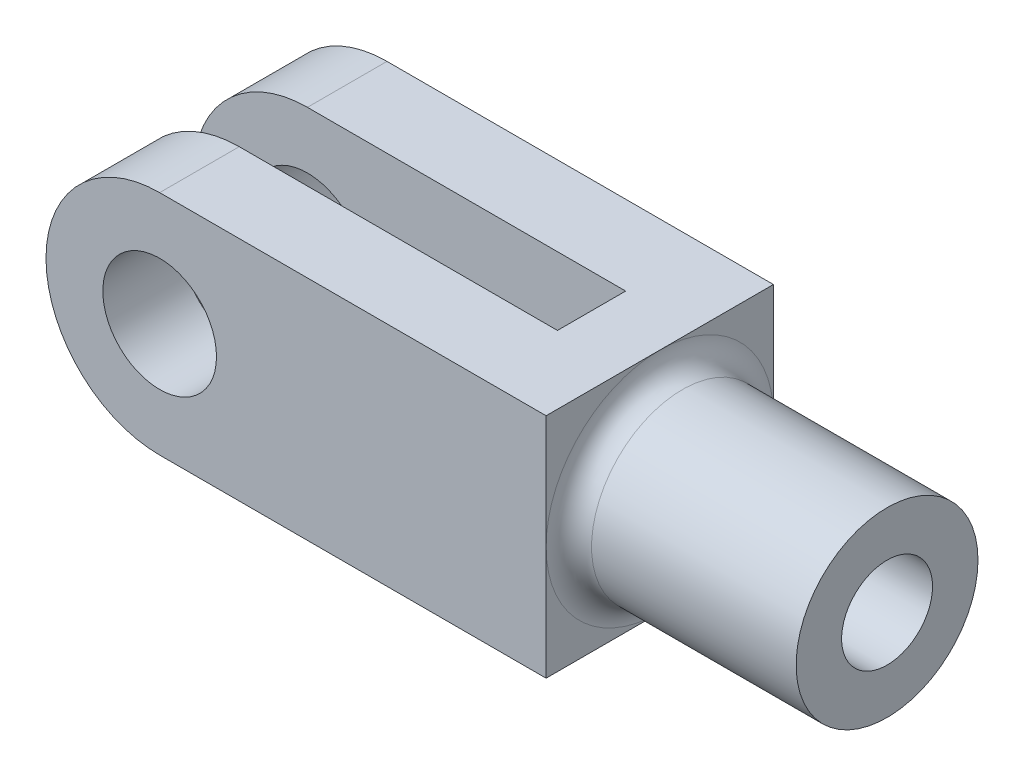
SolidWorks part; units mm, degrees
material "Brass"
ref_plane "Front Plane" through (0, 0, 0) normal (0, 0, 1) x (1, 0, 0)
ref_plane "Top Plane" through (0, 0, 0) normal (0, 1, 0) x (1, 0, 0)
ref_plane "Right Plane" through (0, 0, 0) normal (1, 0, 0) x (0, 0, -1)
sketch "Sketch1" plane through (0, 0, 0) normal (0, 0, 1) x (1, 0, 0)
  line L0 (0, 0) -> (10689.6136, 0) construction
  line L1 (0, 0) -> (0, -10689.6136) construction
  line L3 (17, 5) -> (0, 5)
  line L4 (17, 5) -> (17, -5)
  line L5 (17, -5) -> (0, -5)
  line L7 (17, 5) -> (0, -5) construction
  line L8 (17, -5) -> (0, 5) construction
  circle A0 centre (0, 0) radius 2.5
  arc A1 (0, -5) -> (0, 5) centre (0, 0) cw
  point P7 (8.5, 0)
  point P13 (17, 0)
  dimension "D1" = 5
  dimension "D2" = 17
  dimension "D3" = 10
extrude "Boss-Extrude1" add sketch "Sketch1" along normal mid plane 10 contours A1 L5 L4 L3 A0 region at (7.1805, 0, 0)
sketch "Sketch2" plane through (0, 0, 0) normal (0, 1, 0) x (1, 0, 0)
  line L0 (0, 0) -> (-50000, 0) construction
  line L1 (-5, 5) -> (-5, -5) construction
  line L2 (14, 1.5) -> (-5, 1.5)
  line L3 (14, 1.5) -> (14, -1.5)
  line L4 (14, -1.5) -> (-5, -1.5)
  line L5 (-5, 1.5) -> (-5, -1.5)
  line L6 (14, 1.5) -> (-5, -1.5) construction
  line L7 (14, -1.5) -> (-5, 1.5) construction
  point P3 (4.5, 0)
  dimension "D1" = 3
  dimension "D2" = 19
extrude "Cut-Extrude1" cut sketch "Sketch2" against normal through all both and the other way through all
sketch "Sketch3" plane through (17, 0, 0) normal (1, 0, 0) x (0, 0, -1)
  circle A0 centre (0, 0) radius 2
  circle A1 centre (0, 0) radius 4
  dimension "D1" = 8
  dimension "D2" = 4
extrude "Boss-Extrude2" add sketch "Sketch3" along normal blind 10 contours A1 A0 region at (17, 0, 3.8869)
cosmetic thread "Cosmetic Thread1" parameters "D2"=5
fillet "Fillet1" radius 1 1 edges at (17, 0, -4)
